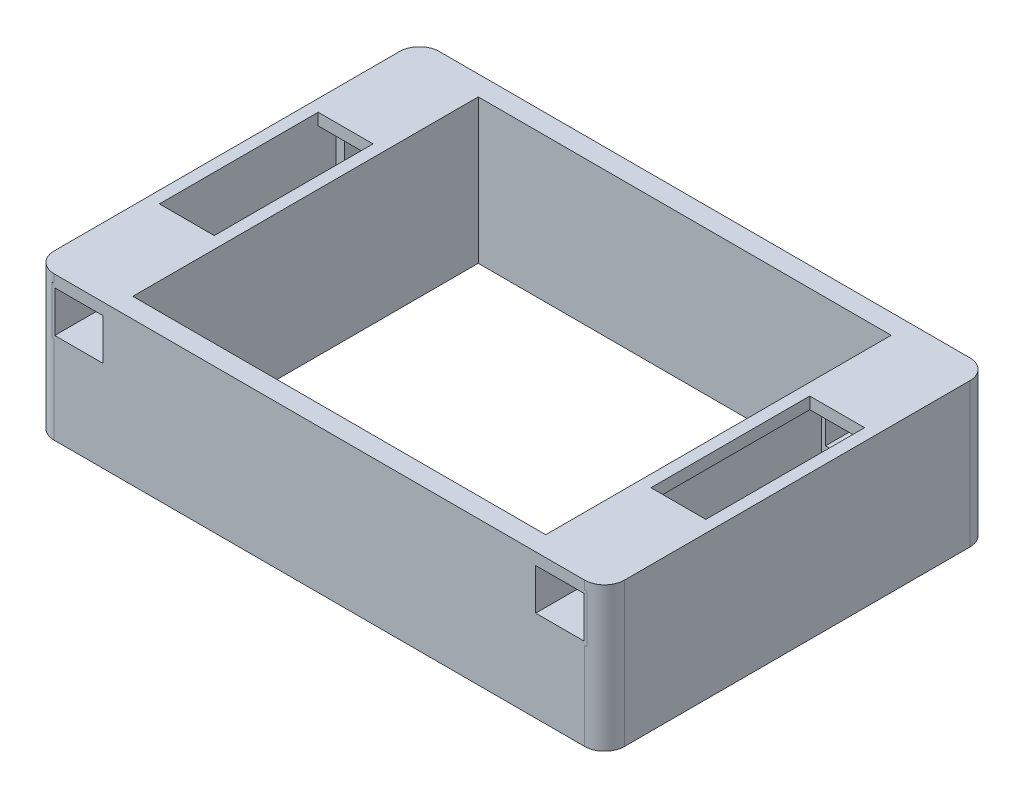
SolidWorks part; units mm, degrees
ref_plane "Alzado" through (0, 0, 0) normal (0, 0, 1) x (1, 0, 0)
ref_plane "Planta" through (0, 0, 0) normal (0, 1, 0) x (1, 0, 0)
ref_plane "Vista lateral" through (0, 0, 0) normal (1, 0, 0) x (0, 0, -1)
sketch "Croquis1" plane through (0, 0, 0) normal (0, 0, 1) x (1, 0, 0)
  line L0 (-8.5, 0) -> (8.5, 0) construction
  line L2 (57, 8.2) -> (57, -26)
  line L3 (57, -26) -> (-57, -26)
  line L4 (-57, 8.2) -> (-57, -26)
  line L5 (30.4, -16) -> (15.6, -16) construction
  line L7 (57, 8.2) -> (-57, 8.2)
  line L8 (47, 0) -> (47, -16) construction
  arc A0 (35, 3.2) -> (34, 3.2) centre (34.5, 3.2) ccw construction
  point P0 (0, 0)
  dimension "D1" = 5
  dimension "D2" = 10
  dimension "D3" = 10
extrude "Saliente-Extruir1" add sketch "Croquis1" against normal blind 97
shell "Vaciado1" thickness 5 removed face at (0, -26, -48.5)
sketch "Croquis2" plane through (0, 0, -97) normal (0, 0, -1) x (-1, 0, 0)
  line L0 (57, 8.2) -> (67.3347, 8.2)
  line L1 (67.3347, 8.2) -> (67.3347, -3.9674)
  line L2 (71.8143, 8.2) -> (71.8143, 10.2965)
  line L3 (67.3347, -26) -> (57, -26)
  line L4 (57, 8.2) -> (57, -26) construction
  line L5 (67.3347, -3.9674) -> (57, -3.9674)
  line L6 (67.3347, 8.2) -> (71.8143, 8.2)
  line L7 (71.8143, 8.2) -> (71.8143, -26)
  line L8 (71.8143, -26) -> (67.3347, -26)
  line L9 (0, 8.2) -> (0, -26) construction
  line L10 (-57, 8.2) -> (57, 8.2) construction
  line L11 (57, -26) -> (-57, -26) construction
  line L12 (71.8143, 10.2965) -> (-71.8143, 10.2965)
  line L13 (67.3347, 8.2) -> (-67.3347, 8.2)
  line L14 (-71.8143, -26) -> (-67.3347, -26)
  line L15 (-71.8143, 8.2) -> (-71.8143, -26)
  line L16 (-67.3347, 8.2) -> (-71.8143, 8.2)
  line L17 (-67.3347, -3.9674) -> (-57, -3.9674)
  line L18 (-67.3347, -26) -> (-57, -26)
  line L19 (-71.8143, 8.2) -> (-71.8143, 10.2965)
  line L20 (-67.3347, 8.2) -> (-67.3347, -3.9674)
  line L21 (-57, 8.2) -> (-67.3347, 8.2)
  point P21 (0, 10.2965)
  line M5 (57, -26) -> (57, 8.2)
  line M6 (57, 8.2) -> (-57, 8.2)
  line M7 (-57, 8.2) -> (-57, -26)
extrude "Saliente-Extruir2" add sketch "Croquis2" against normal through all contours L8 L7 L6 L1 L5 L3 M5 | L19 L16 L13 L0 L6 L2 L12 M6 | L20 L16 L15 L14 L18 L17 M7 region at (0, 9.2483, -97) region at (-65.1466, -12.5368, -97) region at (65.1466, -12.5368, -97)
sketch "Croquis3" plane through (0, -26, 0) normal (0, -1, 0) x (1, 0, 0)
  line L0 (0, 0) -> (0, -97) construction
  line L1 (-71.8143, 0) -> (71.8143, 0) construction
  line L2 (-71.8143, -97) -> (71.8143, -97) construction
  line L3 (-52, -5) -> (-71.8143, -5)
  line L4 (-71.8143, 0) -> (-71.8143, -97) construction
  line L5 (-52, -92) -> (-52, -5) construction
  line L6 (-68.8143, -68.5) -> (-55, -68.5)
  line L7 (-68.8143, -68.5) -> (-68.8143, -28.5)
  line L8 (-68.8143, -28.5) -> (-55, -28.5)
  line L9 (-55, -68.5) -> (-55, -28.5)
  line L10 (-68.8143, -68.5) -> (-55, -28.5) construction
  line L11 (-68.8143, -28.5) -> (-55, -68.5) construction
  line L12 (-71.8143, -48.5) -> (71.8143, -48.5) construction
  line L13 (71.8143, 0) -> (71.8143, -97) construction
  line L14 (68.8143, -28.5) -> (55, -68.5) construction
  line L15 (68.8143, -68.5) -> (55, -28.5) construction
  line L16 (55, -68.5) -> (55, -28.5)
  line L17 (68.8143, -28.5) -> (55, -28.5)
  line L18 (68.8143, -68.5) -> (68.8143, -28.5)
  line L19 (68.8143, -68.5) -> (55, -68.5)
  point P11 (-61.9071, -48.5)
  point P28 (61.9071, -48.5)
  dimension "D1" = 3
  dimension "D2" = 3
  dimension "D3" = 40
extrude "Cortar-Extruir1" cut sketch "Croquis3" against normal up to next contours L6 L9 L8 L7 | L19 L18 L17 L16 region at (-61.9071, -26, -48.5) region at (61.9071, -26, -48.5)
fillet "Redondeo2" radius 5 4 edges at (71.8143, -7.8517, -97) (-71.8143, -7.8517, -97) (71.8143, -7.8517, 0) (-71.8143, -7.8517, 0)
sketch "Croquis5" plane through (-71.8143, 0, 0) normal (-1, 0, 0) x (0, 0, 1)
  line L0 (-5, -10.6991) -> (2.7, -10.6991)
  line L2 (-5, -26) -> (-5, 10.2965) construction
  line L3 (2.7, -10.6991) -> (2.7, -23.7895)
  line L4 (2.7, -23.7895) -> (-5, -23.7895)
  line L5 (-5, -23.7895) -> (-5, -10.6991)
  line L6 (-48.5, -26) -> (-48.5, 10.2965) construction
  line L7 (-5, -26) -> (-92, -26) construction
  line L8 (-5, 10.2965) -> (-92, 10.2965) construction
  line L9 (-92, -23.7895) -> (-92, -10.6991)
  line L10 (-92, -10.6991) -> (-99.7, -10.6991)
  line L11 (-99.7, -10.6991) -> (-99.7, -23.7895)
  line L12 (-99.7, -23.7895) -> (-92, -23.7895)
sketch "Croquis6" plane through (0, 0, -97) normal (0, 0, -1) x (-1, 0, 0)
  line L0 (-67.3347, 8.2) -> (-57, -3.9674) construction
  line L1 (67.3347, 8.2) -> (57, -3.9674) construction
  line L2 (-60.6173, 0) -> (60.6173, 0)
  line L3 (-60.6173, 8.2) -> (-60.6173, -3.9674) construction
  line L4 (-57, 8.2) -> (-66.8143, 8.2) construction
  line L5 (-66.8143, -3.9674) -> (-57, -3.9674) construction
  line L6 (60.6173, 8.2) -> (60.6173, -3.9674) construction
  line L7 (66.8143, 8.2) -> (57, 8.2) construction
  line L8 (66.8143, -3.9674) -> (57, -3.9674) construction
  line L9 (0, 10.2965) -> (0, -26) construction
  line L10 (-66.7673, -3.0837) -> (-54.4673, -3.0837)
  line L11 (-66.7673, -3.0837) -> (-66.7673, 7.3163)
  line L12 (-66.7673, 7.3163) -> (-54.4673, 7.3163)
  line L13 (-54.4673, -3.0837) -> (-54.4673, 7.3163)
  line L14 (-60.6173, 7.3163) -> (-60.6173, -3.0837) construction
  line L15 (-66.7673, 2.1163) -> (-54.4673, 2.1163) construction
  line L16 (66.8143, 10.2965) -> (-66.8143, 10.2965) construction
  line L17 (66.8143, -26) -> (-66.8143, -26) construction
  line L18 (66.7673, 2.1163) -> (54.4673, 2.1163) construction
  line L19 (60.6173, 7.3163) -> (60.6173, -3.0837) construction
  line L20 (60.6173, 8.2) -> (60.6173, -3.9674) construction
  line L21 (67.3347, 8.2) -> (57, -3.9674) construction
  line L22 (54.4673, -3.0837) -> (54.4673, 7.3163)
  line L23 (66.7673, 7.3163) -> (54.4673, 7.3163)
  line L24 (66.7673, -3.0837) -> (66.7673, 7.3163)
  line L25 (66.7673, -3.0837) -> (54.4673, -3.0837)
  point P8 (62.1673, 2.1163)
  point P14 (0, 0)
  point P28 (-60.6173, 2.1163)
  point P46 (60.6173, 2.1163)
  dimension "D1" = 1.55
  dimension "D2" = 12.3
  dimension "D3" = 10.4
extrude "Cortar-Extruir3" cut sketch "Croquis6" against normal through all contours L22 L23 L24 L25 | L11 L12 L13 L10
sketch "Croquis7" plane through (0, 0, -97) normal (0, 0, -1) x (-1, 0, 0)
  line L0 (-57, 7.3163) -> (-57, 8.2)
  line L1 (-54.4673, -3.0837) -> (-66.6673, -3.0837)
  line L2 (-54.4673, -3.0837) -> (-54.4673, 7.325)
  line L3 (-54.4673, 7.325) -> (-66.6673, 7.325)
  line L4 (-66.6673, -3.0837) -> (-66.6673, 7.325)
  line L5 (-57, 8.2) -> (-67.3347, 8.2)
  line L6 (-67.3347, 8.2) -> (-67.3347, -3.9674)
  line L7 (-67.3347, -3.9674) -> (-57, -3.9674)
  line L8 (-57, -3.9674) -> (-57, -3.0837)
  line L9 (57, 7.3163) -> (57, 8.2)
  line L10 (54.4673, -3.0837) -> (66.6673, -3.0837)
  line L11 (54.4673, -3.0837) -> (54.4673, 7.3163)
  line L12 (54.4673, 7.3163) -> (66.6673, 7.3163)
  line L13 (66.6673, -3.0837) -> (66.6673, 7.3163)
  line L14 (57, 8.2) -> (67.3347, 8.2)
  line L15 (67.3347, 8.2) -> (67.3347, -3.9674)
  line L16 (67.3347, -3.9674) -> (57, -3.9674)
  line L17 (57, -3.9674) -> (57, -3.0837)
  line M3 (57, -3.9674) -> (57, -3.0837)
  line M7 (57, 7.3163) -> (57, 8.2)
  line M8 (57, 8.2) -> (66.8143, 8.2)
  line M12 (-66.8143, 8.2) -> (-57, 8.2)
  line M13 (-57, 8.2) -> (-57, 7.3163)
  line M17 (-57, -3.0837) -> (-57, -3.9674)
  line M18 (-57, -3.9674) -> (-66.8143, -3.9674)
  line M22 (66.8143, -3.9674) -> (57, -3.9674)
  dimension "D1" = 12.2
  dimension "D2" = 12.2
extrude "Saliente-Extruir3" add sketch "Croquis7" against normal through all contours L16 L15 L14 L12 L13 L10 M8 M7 M3 M22 | L6 L7 L1 L4 L3 L5 M18 M17 M13 M12 region at (61.8337, 7.4847, -97) region at (-57.1596, 7.7582, -97)
sketch "Croquis8" plane through (0, 10.2965, 0) normal (0, 1, 0) x (1, 0, 0)
  line L1 (-68.8143, 68.5) -> (-55, 68.5)
  line L2 (-68.8143, 68.5) -> (-68.8143, 28.5)
  line L3 (-68.8143, 28.5) -> (-55, 28.5)
  line L4 (-55, 68.5) -> (-55, 28.5)
  line L5 (55, 68.5) -> (68.8143, 68.5)
  line L6 (55, 68.5) -> (55, 28.5)
  line L7 (55, 28.5) -> (68.8143, 28.5)
  line L8 (68.8143, 68.5) -> (68.8143, 28.5)
extrude "Cortar-Extruir4" cut sketch "Croquis8" against normal through all
sketch "Croquis9" plane through (0, 3.2, 0) normal (0, -1, 0) x (1, 0, 0)
  line L0 (52, -92) -> (52, -5) construction
  line L1 (-52, -5) -> (52, -5)
  line L2 (-52, -5) -> (-52, -92)
  line L3 (-52, -92) -> (52, -92)
  line L4 (52, -5) -> (52, -92)
extrude "Cortar-Extruir5" cut sketch "Croquis9" against normal blind 10
ref_plane "Plano1" through (54.4673, -3.0837, -97) normal (-1, 0, 0) x (0, 0, 1)
sketch "Croquis11" plane through (0, -26, 0) normal (0, -1, 0) x (1, 0, 0)
  line L1 (55, -28.5) -> (53.5, -28.5)
  line L2 (55, -28.5) -> (55, -68.4995)
  line L3 (55, -68.4995) -> (53.5, -68.4995)
  line L4 (53.5, -28.5) -> (53.5, -68.4995)
  line L5 (-55, -68.5) -> (-53.5, -68.5)
  line L6 (-55, -68.5) -> (-55, -28.5)
  line L7 (-55, -28.5) -> (-53.5, -28.5)
  line L8 (-53.5, -68.5) -> (-53.5, -28.5)
  dimension "D1" = 1.5
  dimension "D2" = 1.5
extrude "Cortar-Extruir6" cut sketch "Croquis11" against normal up to vertex (33.3163 mm away) up to point (-55, 7.3163, -28.5)
sketch "Croquis13" plane through (0, -26, 0) normal (0, -1, 0) x (1, 0, 0)
  line L1 (-68.8143, -28.5) -> (-53.5, -28.5)
  line L2 (-68.8143, -28.5) -> (-68.8143, -24)
  line L3 (-68.8143, -24) -> (-53.5, -24)
  line L4 (-53.5, -28.5) -> (-53.5, -24)
  line L5 (-68.8143, -68.5) -> (-53.5, -68.5)
  line L6 (-68.8143, -68.5) -> (-68.8143, -73)
  line L7 (-68.8143, -73) -> (-53.5, -73)
  line L8 (-53.5, -68.5) -> (-53.5, -73)
  line L9 (53.5, -28.5) -> (68.8143, -28.5)
  line L10 (53.5, -28.5) -> (53.5, -24)
  line L11 (53.5, -24) -> (68.8143, -24)
  line L12 (68.8143, -28.5) -> (68.8143, -24)
  line L13 (53.5, -68.4995) -> (68.8143, -68.4995)
  line L14 (53.5, -68.4995) -> (53.5, -72.9995)
  line L15 (53.5, -72.9995) -> (68.8143, -72.9995)
  line L16 (68.8143, -68.4995) -> (68.8143, -72.9995)
  dimension "D1" = 4.5
  dimension "D2" = 4.5
  dimension "D3" = 4.5
  dimension "D4" = 4.5
extrude "Cortar-Extruir7" cut sketch "Croquis13" against normal up to surface (33.3163 mm away) up to face at (-58.4616, 7.3163, -48.5)
